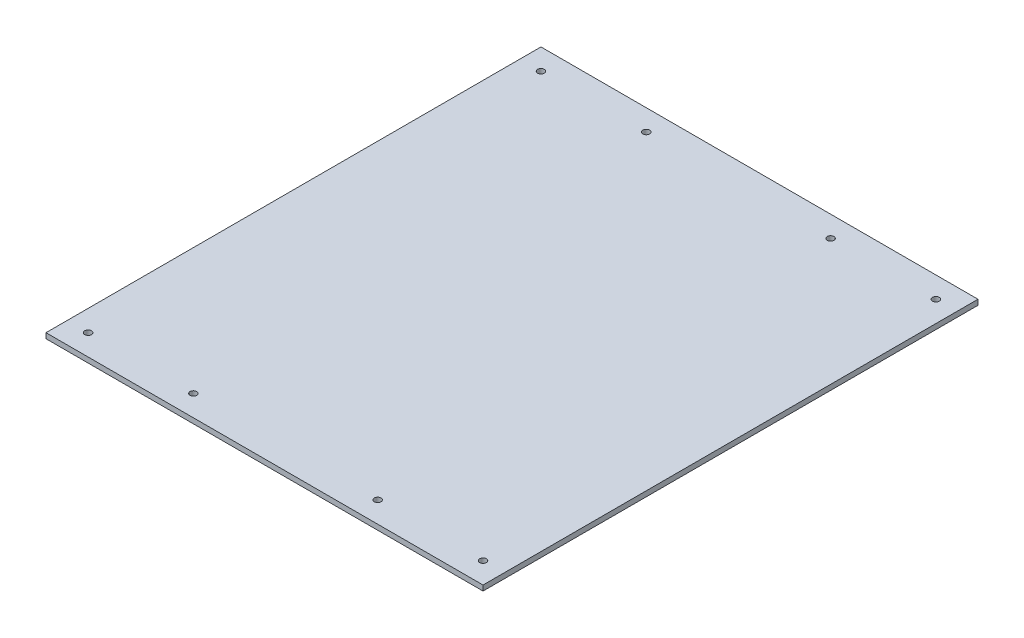
SolidWorks part; units mm, degrees
ref_plane "Front Plane" through (0, 0, 0) normal (0, 0, 1) x (1, 0, 0)
ref_plane "Top Plane" through (0, 0, 0) normal (0, 1, 0) x (1, 0, 0)
ref_plane "Right Plane" through (0, 0, 0) normal (1, 0, 0) x (0, 0, -1)
sketch "Sketch1" plane through (0, 0, 0) normal (0, 1, 0) x (1, 0, 0)
  line L1 (-207.5, -235) -> (207.5, -235)
  line L2 (-207.5, -235) -> (-207.5, 235)
  line L3 (-207.5, 235) -> (207.5, 235)
  line L4 (207.5, -235) -> (207.5, 235)
  line L5 (-207.5, -235) -> (207.5, 235) construction
  line L6 (-207.5, 235) -> (207.5, -235) construction
  point P0 (0, 0)
  dimension "D1" = 415
  dimension "D2" = 470
extrude "Boss-Extrude1" add sketch "Sketch1" along normal blind 5
hole_wizard "M6 Clearance Hole1" positions "Sketch3" profile "Sketch2" hole size "M6" standard "ANSI Metric"
sketch "Sketch3" plane through (0, 5, 0) normal (0, 1, 0) x (1, 0, 0)
  line L0 (-1089.4391, -215) -> (48910.5609, -215) construction
  line L1 (-1065.6521, 215) -> (48934.3479, 215) construction
  line L2 (-187.5, -977.1645) -> (-187.5, 49022.8355) construction
  line L3 (-87.5, -976.213) -> (-87.5, 49023.787) construction
  line L4 (87.5, -978.116) -> (87.5, 49021.884) construction
  line L5 (187.5, -979.0674) -> (187.5, 49020.9326) construction
  line L6 (-207.5, -235) -> (207.5, -235) construction
  line L7 (207.5, 235) -> (-207.5, 235) construction
  line L8 (-207.5, 235) -> (-207.5, -235) construction
  line L9 (207.5, -235) -> (207.5, 235) construction
  point P46 (-187.5, 215)
  point P47 (-87.5, 215)
  point P49 (87.5, 215)
  point P51 (187.5, 215)
  point P53 (-187.5, -215)
  point P55 (-87.5, -215)
  point P57 (87.5, -215)
  point P59 (187.5, -215)
  dimension "D1" = 20
  dimension "D2" = 20
  dimension "D3" = 20
  dimension "D4" = 20
  dimension "D5" = 100
  dimension "D6" = 100
sketch "Sketch2" plane through (-187.5, 5, -215) normal (1, 0, 0) x (0, 0, 1)
  line L0 (0, 0) -> (0, 11.9228)
  line L1 (0, 11.9228) -> (3.2, 10)
  line L2 (3.2, 10) -> (3.2, 0)
  line L5 (3.2, 0) -> (0, 0)
  line L10 (0, 11.9228) -> (-3.2, 10) construction
  line L11 (0, -6.35) -> (0, 107.95) construction
  dimension "Hole Dia." = 6.4
  dimension "Hole Depth" = 10
  dimension "Drill Angle" = 118
